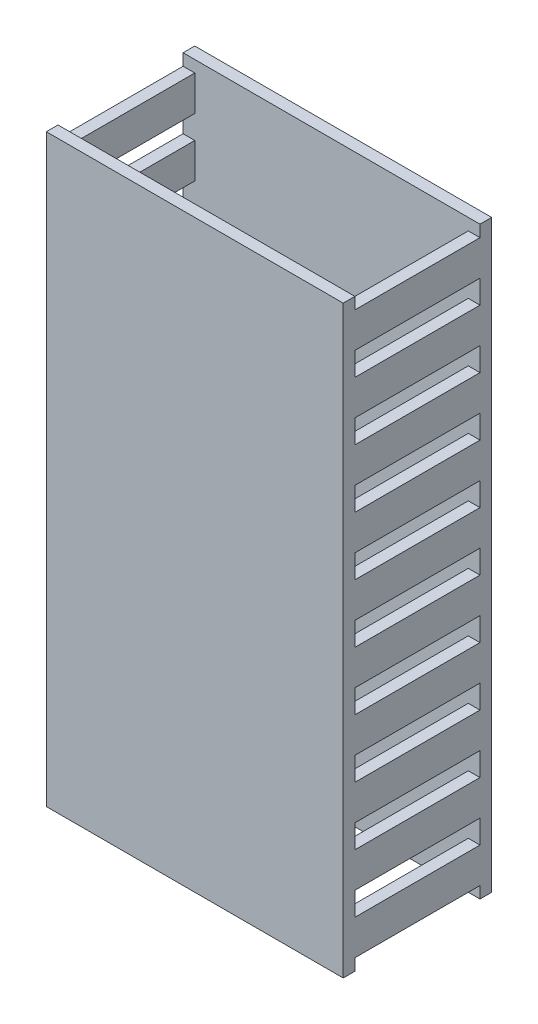
SolidWorks part; units mm, degrees
ref_plane "Front Plane" through (0, 0, 0) normal (0, 0, 1) x (1, 0, 0)
ref_plane "Top Plane" through (0, 0, 0) normal (0, 1, 0) x (1, 0, 0)
ref_plane "Right Plane" through (0, 0, 0) normal (1, 0, 0) x (0, 0, -1)
sketch "Sketch1" plane through (0, 0, 0) normal (0, 1, 0) x (1, 0, 0)
  line L0 (0, 25.4) -> (50.8, 0) construction
  line L1 (0, 0) -> (50.8, 0)
  line L2 (0, 0) -> (0, 25.4)
  line L3 (0, 25.4) -> (50.8, 25.4)
  line L4 (50.8, 0) -> (50.8, 25.4)
  line L6 (2, 23.4) -> (48.8, 23.4)
  line L7 (2, 23.4) -> (2, 2)
  line L8 (2, 2) -> (48.8, 2)
  line L9 (48.8, 23.4) -> (48.8, 2)
  line L10 (2, 23.4) -> (48.8, 2) construction
  line L11 (2, 2) -> (48.8, 23.4) construction
  point P5 (25.4, 12.7)
  dimension "D1" = 50.8
  dimension "D2" = 25.4
  dimension "D3" = 2
  dimension "D4" = 2
extrude "Boss-Extrude1" add sketch "Sketch1" along normal mid plane 100
sketch "Sketch2" plane through (50.8, 0, 0) normal (1, 0, 0) x (0, 0, -1)
  line L0 (2, 50) -> (2, -50) construction
  line L1 (2, 50) -> (2, -50)
  line L2 (23.4, 50) -> (23.4, -50) construction
  line L3 (23.4, 50) -> (23.4, -50)
  line L4 (23.4, 0) -> (2, 0) construction
  line L6 (2, 2) -> (23.4, 2)
  line L7 (2, 2) -> (2, -2)
  line L8 (2, -2) -> (23.4, -2)
  line L9 (23.4, 2) -> (23.4, -2)
  line L10 (2, 2) -> (23.4, -2) construction
  line L11 (2, -2) -> (23.4, 2) construction
  point P6 (12.7, 0)
  dimension "D1" = 4
extrude "Cut-Extrude1" cut sketch "Sketch2" against normal through all contours L1 L8 L3 L6 region at (50.8, 0, -12.7)
pattern_linear "LPattern1" count 6 spacing 10 along (0, -1, 0) count 6 spacing 10 along (0, 1, 0) of "Cut-Extrude1"
